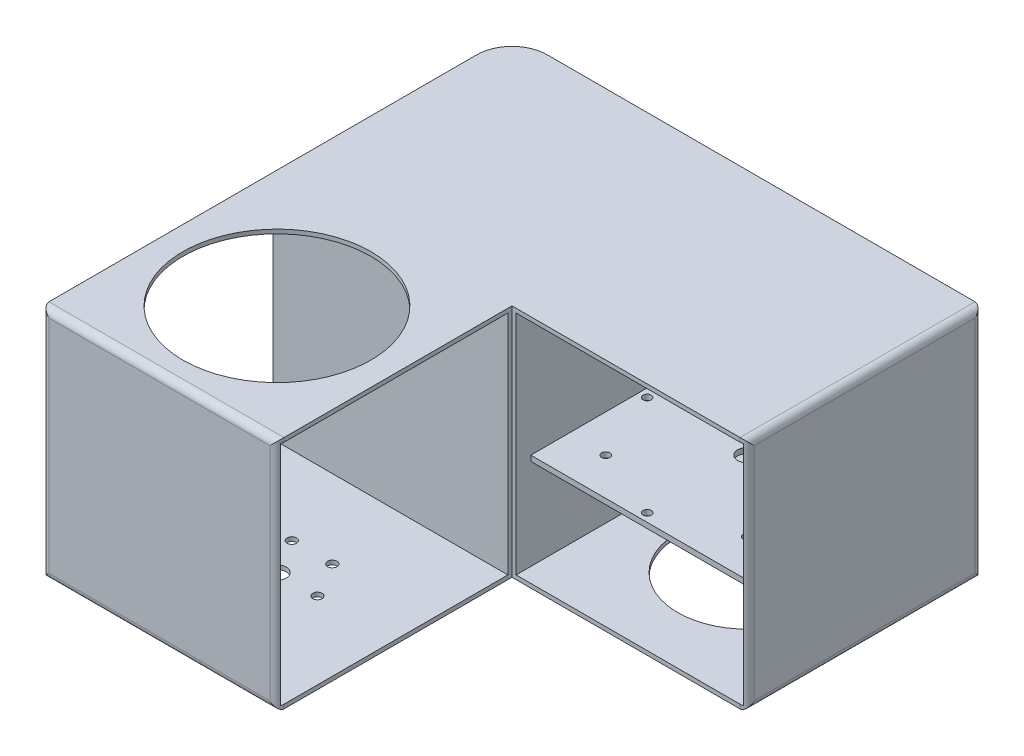
SolidWorks part; units mm, degrees
ref_plane "前视基准面" through (0, 0, 0) normal (0, 0, 1) x (1, 0, 0)
ref_plane "上视基准面" through (0, 0, 0) normal (0, 1, 0) x (1, 0, 0)
ref_plane "右视基准面" through (0, 0, 0) normal (1, 0, 0) x (0, 0, -1)
other "Configuration Table"
sketch "草图1" plane through (0, 0, 0) normal (0, 1, 0) x (1, 0, 0)
  line L0 (-50, 50) -> (-50, 150)
  line L2 (-50, 50) -> (-50, -50)
  line L3 (-50, -50) -> (50, -50)
  line L4 (50, 50) -> (50, -50)
  line L5 (-50, 50) -> (50, -50) construction
  line L6 (-50, -50) -> (50, 50) construction
  line L7 (-50, 150) -> (50, 150)
  line L9 (50, 150) -> (150, 150)
  line L10 (150, 150) -> (150, 50)
  line L11 (150, 50) -> (50, 50)
  point P0 (0, 0)
  dimension "D1" = 100
  dimension "D2" = 100
  dimension "D3" = 100
  dimension "D4" = 100
extrude "凸台-拉伸1" add sketch "草图1" along normal blind 100
sketch "草图2" plane through (0, 100, 0) normal (0, 1, 0) x (1, 0, 0)
  circle A0 centre (0, 0) radius 40
extrude "切除-拉伸1" cut sketch "草图2" against normal blind 90
sketch "草图9" plane through (-50, 0, 0) normal (-1, 0, 0) x (0, 0, 1)
  line L12 (-48.25, 98.25) -> (48.25, 98.25)
  line L13 (-48.25, 98.25) -> (-48.25, 1.75)
  line L14 (-48.25, 1.75) -> (48.25, 1.75)
  line L15 (48.25, 98.25) -> (48.25, 1.75)
  line L16 (-48.25, 98.25) -> (48.25, 1.75) construction
  line L17 (-48.25, 1.75) -> (48.25, 98.25) construction
  dimension "D1" = 96.5
  dimension "D2" = 96.5
extrude "切除-拉伸3" cut sketch "草图9" against normal blind 100
sketch "草图15" plane through (0, 0, -150) normal (0, 0, -1) x (-1, 0, 0)
  circle A2 centre (-89.0234, 21) radius 4
  circle A3 centre (-89.0234, 79) radius 4
extrude "凸台-拉伸4" add sketch "草图15" along normal blind 5
sketch "草图16" plane through (0, 0, 0) normal (0, -1, 0) x (1, 0, 0)
  circle A0 centre (100, -100) radius 29.5
extrude "切除-拉伸5" cut sketch "草图16" against normal blind 5
sketch "草图18" plane through (-50, 0, 0) normal (-1, 0, 0) x (0, 0, 1)
  point P0 (0, 50)
sketch "草图19" plane through (0, 0, -50) normal (0, 0, 1) x (1, 0, 0)
  line L0 (50, 50) -> (150, 50) construction
  line L1 (50, 100) -> (50, 0) construction
  line L2 (150, 100) -> (150, 0) construction
  line L3 (100, 0) -> (100, 100) construction
  line L4 (50, 0) -> (150, 0) construction
  line L5 (50, 100) -> (150, 100) construction
  line L7 (51.75, 98.25) -> (148.25, 98.25)
  line L8 (51.75, 98.25) -> (51.75, 1.75)
  line L9 (51.75, 1.75) -> (148.25, 1.75)
  line L10 (148.25, 98.25) -> (148.25, 1.75)
  line L11 (51.75, 98.25) -> (148.25, 1.75) construction
  line L12 (51.75, 1.75) -> (148.25, 98.25) construction
  point P12 (100, 50)
  dimension "D1" = 96.5
  dimension "D2" = 96.5
extrude "切除-拉伸8" cut sketch "草图19" against normal blind 99
sketch "草图20" plane through (0, 1.75, 0) normal (0, 1, 0) x (1, 0, 0)
  circle A1 centre (17.25, 0) radius 2
  circle A2 centre (8.625, -14.9389) radius 2
  circle A3 centre (-8.625, -14.9389) radius 2
  circle A4 centre (-17.25, 0) radius 2
  circle A5 centre (-8.625, 14.9389) radius 2
  circle A6 centre (8.625, 14.9389) radius 2
  circle A7 centre (0, 0) radius 4
  point P17 (0, 0)
  dimension "D2" = 6
extrude "切除-拉伸9" cut sketch "草图20" against normal blind 1.75
sketch "草图23" plane through (0, 100, 0) normal (0, 1, 0) x (1, 0, 0)
  line L0 (50, 50) -> (50, 150) construction
  line L1 (150, 150) -> (-50, 150) construction
  line L2 (50, 100) -> (100, 100) construction
  line L3 (100, 100) -> (150, 100) construction
  line L4 (100, 100) -> (100, 150) construction
  line L5 (150, 50) -> (150, 150) construction
  line L7 (54, 146) -> (146, 146)
  line L8 (54, 146) -> (54, 54)
  line L9 (54, 54) -> (146, 54)
  line L10 (146, 146) -> (146, 54)
  line L11 (54, 146) -> (146, 54) construction
  line L12 (54, 54) -> (146, 146) construction
  dimension "D1" = 50
  dimension "D2" = 92
  dimension "D3" = 92
extrude "凸台-拉伸5" add sketch "草图23" against normal blind 57.3
sketch "草图24" plane through (0, 42.7, 0) normal (0, -1, 0) x (1, 0, 0)
  circle A1 centre (100, -57.5) radius 1.75
  circle A2 centre (130.052, -69.948) radius 1.75
  circle A3 centre (142.5, -100) radius 1.75
  circle A4 centre (130.052, -130.052) radius 1.75
  circle A5 centre (100, -142.5) radius 1.75
  circle A6 centre (69.948, -130.052) radius 1.75
  circle A7 centre (57.5, -100) radius 1.75
  circle A8 centre (69.948, -69.948) radius 1.75
  circle A9 centre (100, -100) radius 4
  point P21 (100, -100)
  dimension "D2" = 3.5
  dimension "D3" = 8
extrude "切除-拉伸10" cut sketch "草图24" against normal blind 3
sketch "草图27" plane through (0, 100, 0) normal (0, 1, 0) x (1, 0, 0)
  line L1 (52.6529, 145.1806) -> (144.6529, 145.1806)
  line L2 (52.6529, 145.1806) -> (52.6529, 53.1806)
  line L3 (52.6529, 53.1806) -> (144.6529, 53.1806)
  line L4 (144.6529, 145.1806) -> (144.6529, 53.1806)
  line L5 (52.6529, 145.1806) -> (144.6529, 53.1806) construction
  line L6 (52.6529, 53.1806) -> (144.6529, 145.1806) construction
  point P0 (98.6529, 99.1806)
  point P5 (0, 0)
  dimension "D1" = 92
  dimension "D2" = 92
extrude "切除-拉伸12" cut sketch "草图27" against normal blind 50 from offset 5 offset against normal yes
fillet "圆角2" radius 3 8 edges at (50, 50, 50) (0, 0, 50) (-50, 50, 50) (0, 100, 50) (150, 100, -100) (150, 50, -50) (150, 50, -150) (150, 0, -100)
fillet "圆角6" radius 15 1 edges at (-50, 50, -150)
